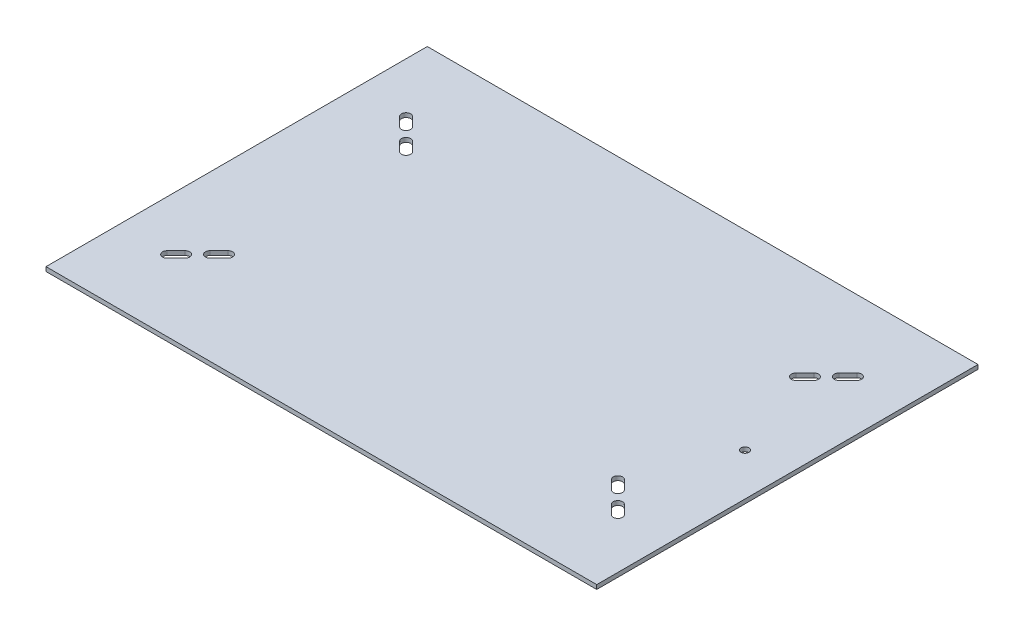
SolidWorks part; units mm, degrees
ref_plane "Front Plane" through (0, 0, 0) normal (0, 0, 1) x (1, 0, 0)
ref_plane "Top Plane" through (0, 0, 0) normal (0, 1, 0) x (1, 0, 0)
ref_plane "Right Plane" through (0, 0, 0) normal (1, 0, 0) x (0, 0, -1)
sketch "Sketch1" plane through (0, 0, 0) normal (0, 1, 0) x (1, 0, 0)
  line L1 (0, 0) -> (330.2, 0)
  line L2 (0, 0) -> (0, -228.6)
  line L3 (0, -228.6) -> (330.2, -228.6)
  line L4 (330.2, 0) -> (330.2, -228.6)
  dimension "D1" = 330.2
  dimension "D2" = 228.6
extrude "base plate" add sketch "Sketch1" against normal blind 2.54
sketch "center lines" plane through (0, 0, 0) normal (0, 1, 0) x (1, 0, 0)
  line L0 (165.1, 0) -> (165.1, -228.6) construction
  line L1 (330.2, 0) -> (0, 0) construction
  line L2 (0, -228.6) -> (330.2, -228.6) construction
  line L3 (0, -114.3) -> (330.2, -114.3) construction
  line L4 (0, 0) -> (0, -228.6) construction
  line L5 (330.2, -228.6) -> (330.2, 0) construction
sketch "Sketch3" plane through (0, 0, 0) normal (0, 1, 0) x (1, 0, 0)
  line L0 (21.0672, -185.8525) -> (30.0475, -194.8328)
  line L1 (30.0475, -194.8328) -> (60.5804, -164.2999)
  line L2 (60.5804, -164.2999) -> (51.6001, -155.3196)
  line L3 (51.6001, -155.3196) -> (21.0672, -185.8525)
  line L4 (29.9612, -185.9388) -> (35.3494, -180.5506) construction
  line L5 (28.0167, -183.9942) -> (33.4048, -178.6061)
  line L6 (31.9058, -187.8833) -> (37.2939, -182.4952)
  line L7 (0, -228.6) -> (330.2, -228.6) construction
  line L8 (48.2187, -167.6813) -> (42.8306, -173.0694) construction
  line L9 (50.1633, -169.6258) -> (44.7751, -175.014)
  line L10 (165.1, 0) -> (165.1, -228.6) construction
  line L11 (0, -114.3) -> (330.2, -114.3) construction
  line L12 (60.5804, -64.3001) -> (51.6001, -73.2804)
  line L13 (30.0475, -33.7672) -> (60.5804, -64.3001)
  line L14 (21.0672, -42.7475) -> (30.0475, -33.7672)
  line L15 (51.6001, -73.2804) -> (21.0672, -42.7475)
  line L16 (300.1525, -33.7672) -> (269.6196, -64.3001)
  line L17 (309.1328, -42.7475) -> (300.1525, -33.7672)
  line L18 (278.5999, -73.2804) -> (309.1328, -42.7475)
  line L19 (269.6196, -64.3001) -> (278.5999, -73.2804)
  line L20 (269.6196, -164.2999) -> (278.5999, -155.3196)
  line L21 (300.1525, -194.8328) -> (269.6196, -164.2999)
  line L22 (309.1328, -185.8525) -> (300.1525, -194.8328)
  line L23 (278.5999, -155.3196) -> (309.1328, -185.8525)
  line L24 (46.2742, -165.7367) -> (40.886, -171.1249)
  line L25 (29.9612, -42.6612) -> (35.3494, -48.0494) construction
  line L26 (28.0167, -44.6058) -> (33.4048, -49.9939)
  line L27 (31.9058, -40.7167) -> (37.2939, -46.1048)
  line L28 (48.2187, -60.9187) -> (42.8306, -55.5306) construction
  line L29 (50.1633, -58.9742) -> (44.7751, -53.586)
  line L30 (46.2742, -62.8633) -> (40.886, -57.4751)
  line L31 (300.2388, -42.6612) -> (294.8506, -48.0494) construction
  line L32 (302.1833, -44.6058) -> (296.7952, -49.9939)
  line L33 (298.2942, -40.7167) -> (292.9061, -46.1048)
  line L34 (281.9813, -60.9187) -> (287.3694, -55.5306) construction
  line L35 (280.0367, -58.9742) -> (285.4249, -53.586)
  line L36 (283.9258, -62.8633) -> (289.314, -57.4751)
  line L37 (281.9813, -167.6813) -> (287.3694, -173.0694) construction
  line L38 (280.0367, -169.6258) -> (285.4249, -175.014)
  line L39 (283.9258, -165.7367) -> (289.314, -171.1249)
  line L40 (300.2388, -185.9388) -> (294.8506, -180.5506) construction
  line L41 (302.1833, -183.9942) -> (296.7952, -178.6061)
  line L42 (298.2942, -187.8833) -> (292.9061, -182.4952)
  line L43 (51.6001, -164.2999) -> (51.6001, -155.3196)
  line L44 (60.5804, -164.2999) -> (51.6001, -164.2999)
  line L45 (51.6001, -64.3001) -> (51.6001, -73.2804)
  line L46 (60.5804, -64.3001) -> (51.6001, -64.3001)
  line L47 (278.5999, -64.3001) -> (278.5999, -73.2804)
  line L48 (269.6196, -64.3001) -> (278.5999, -64.3001)
  line L49 (278.5999, -164.2999) -> (278.5999, -155.3196)
  line L50 (269.6196, -164.2999) -> (278.5999, -164.2999)
  arc A0 (28.0167, -183.9942) -> (31.9058, -187.8833) centre (29.9612, -185.9388) ccw
  arc A1 (37.2939, -182.4952) -> (33.4048, -178.6061) centre (35.3494, -180.5506) ccw
  arc A2 (50.1633, -169.6258) -> (46.2742, -165.7367) centre (48.2187, -167.6813) ccw
  arc A3 (40.886, -171.1249) -> (44.7751, -175.014) centre (42.8306, -173.0694) ccw
  arc A4 (28.0167, -44.6058) -> (31.9058, -40.7167) centre (29.9612, -42.6612) cw
  arc A5 (37.2939, -46.1048) -> (33.4048, -49.9939) centre (35.3494, -48.0494) cw
  arc A6 (50.1633, -58.9742) -> (46.2742, -62.8633) centre (48.2187, -60.9187) cw
  arc A7 (40.886, -57.4751) -> (44.7751, -53.586) centre (42.8306, -55.5306) cw
  arc A8 (302.1833, -44.6058) -> (298.2942, -40.7167) centre (300.2388, -42.6612) ccw
  arc A9 (292.9061, -46.1048) -> (296.7952, -49.9939) centre (294.8506, -48.0494) ccw
  arc A10 (280.0367, -58.9742) -> (283.9258, -62.8633) centre (281.9813, -60.9187) ccw
  arc A11 (289.314, -57.4751) -> (285.4249, -53.586) centre (287.3694, -55.5306) ccw
  arc A12 (280.0367, -169.6258) -> (283.9258, -165.7367) centre (281.9813, -167.6813) cw
  arc A13 (289.314, -171.1249) -> (285.4249, -175.014) centre (287.3694, -173.0694) cw
  arc A14 (302.1833, -183.9942) -> (298.2942, -187.8833) centre (300.2388, -185.9388) cw
  arc A15 (292.9061, -182.4952) -> (296.7952, -178.6061) centre (294.8506, -180.5506) cw
  point P29 (32.6553, -183.2447)
  point P36 (45.5246, -170.3754)
  point P44 (32.6553, -45.3553)
  point P51 (45.5246, -58.2246)
  point P58 (297.5447, -45.3553)
  point P65 (284.6754, -58.2246)
  point P72 (284.6754, -170.3754)
  point P79 (297.5447, -183.2447)
  point P84 (37.2939, -178.6061)
  point P85 (40.886, -175.014)
  dimension "D6" = 2.75
  dimension "D10" = 5.08
  dimension "D9" = 2.032
  dimension "D1" = 43.18
  dimension "D2" = 12.7
  dimension "D3" = 45
  dimension "D4" = 99.9998
  dimension "D5" = 226.9998
  dimension "D7" = 7.62
  dimension "D8" = 6.35
extrude "slots" cut sketch "Sketch3" against normal through all contours A5 L27 A4 L26 | L33 A9 L32 A8 | L36 A11 L35 A10 | A13 L39 A12 L38 | A15 L42 A14 L41 | L6 A1 L5 A0 | L24 A3 L9 A2 | L30 A7 L29 A6 region at (32.6553, 0, 45.3553) region at (297.5447, 0, 45.3553) region at (284.6754, 0, 58.2246) region at (284.6754, 0, 170.3754) region at (297.5447, 0, 183.2447)
sketch "location of ESD" plane through (0, 0, 0) normal (0, 1, 0) x (1, 0, 0)
  line L0 (330.2, -228.6) -> (330.2, 0) construction
  line L1 (330.2, 0) -> (0, 0) construction
  point P0 (304.8, -114.3)
  point P3 (330.2, -114.3)
  dimension "D1" = 25.4
  dimension "D2" = 114.3
hole_wizard "ESD connector hole" positions "Sketch6" profile "Sketch7" hole size "#6-32" standard "PEM® Inch" end condition through all
sketch "Sketch6" plane through (0, 0, 0) normal (0, 1, 0) x (1, 0, 0)
  point P0 (304.8, -114.3)
sketch "Sketch7" plane through (304.8, 0, 114.3) normal (1, 0, 0) x (0, 0, 1)
  line L0 (0, 0) -> (0, 2.54)
  line L1 (0, 2.54) -> (2.3812, 2.54)
  line L2 (2.3812, 2.54) -> (2.3812, 0)
  line L5 (2.3812, 0) -> (0, 0)
  line L11 (0, -6.35) -> (0, 107.95) construction
  dimension "Thru Hole Dia." = 4.7625
  dimension "Thru Hole Depth" = 2.54
